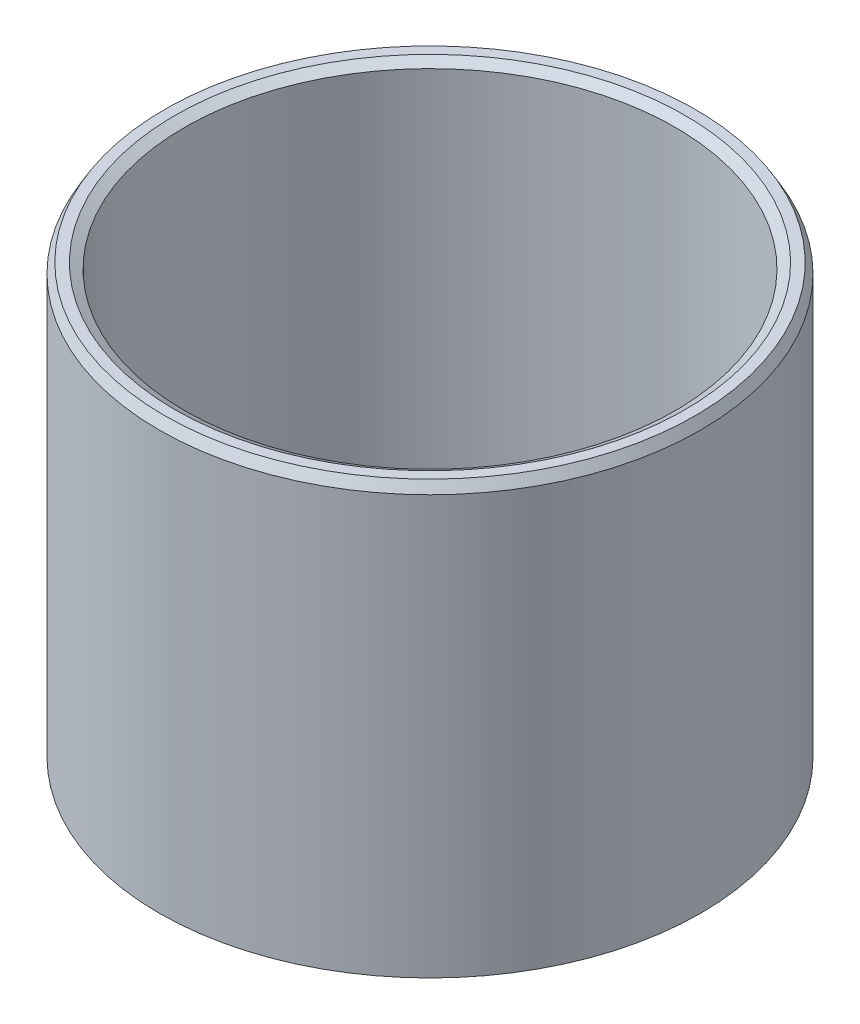
SolidWorks part; units mm, degrees
ref_plane "Front Plane" through (0, 0, 0) normal (0, 0, 1) x (1, 0, 0)
ref_plane "Top Plane" through (0, 0, 0) normal (0, 1, 0) x (1, 0, 0)
ref_plane "Right Plane" through (0, 0, 0) normal (1, 0, 0) x (0, 0, -1)
sketch "Sketch1" plane through (0, 0, 0) normal (0, 1, 0) x (1, 0, 0)
  circle A0 centre (0, 0) radius 52.5
  dimension "SLEEVE_OD" = 105
extrude "Boss-Extrude1" add sketch "Sketch1" along normal blind 84.0536
sketch "Sketch2" plane through (0, 0, 0) normal (0, 1, 0) x (1, 0, 0)
  circle A0 centre (0, 0) radius 47.5609
  dimension "BORE_D" = 95.1217
extrude "Cut-Extrude1" cut sketch "Sketch2" along normal through all
chamfer "Chamfer1" distance 1.8638 angle 30 4 edges at (0, 84.0536, 47.5609) (0, 0, 47.5609) (0, 0, 52.5) (0, 84.0536, 52.5) first distance on face at (0, 84.0536, 47.5609) first distance on face at (0, 0, 47.5609) first distance on face at (0, 84.0536, 52.5)
